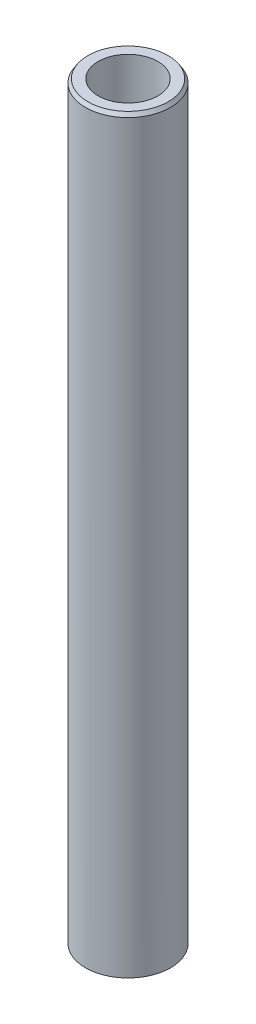
SolidWorks part; units mm, degrees
ref_plane "Front Plane" through (0, 0, 0) normal (0, 0, 1) x (1, 0, 0)
ref_plane "Top Plane" through (0, 0, 0) normal (0, 1, 0) x (1, 0, 0)
ref_plane "Right Plane" through (0, 0, 0) normal (1, 0, 0) x (0, 0, -1)
sketch "Sketch1" plane through (0, 0, 0) normal (0, 1, 0) x (1, 0, 0)
  circle A0 centre (0, 0) radius 25
  dimension "SHAFT_OD" = 50
extrude "Boss-Extrude1" add sketch "Sketch1" along normal blind 441.765
sketch "Sketch2" plane through (0, 0, 0) normal (0, 1, 0) x (1, 0, 0)
  circle A0 centre (0, 0) radius 17.5629
  dimension "BORE_D" = 35.1258
extrude "Cut-Extrude1" cut sketch "Sketch2" along normal through all
chamfer "Chamfer1" distance 2.1713 angle 33.359 2 edges at (0, 441.765, 25) (0, 0, 25) first distance on face at (0, 441.765, 25) first distance on face at (0, 0, 17.5629)
